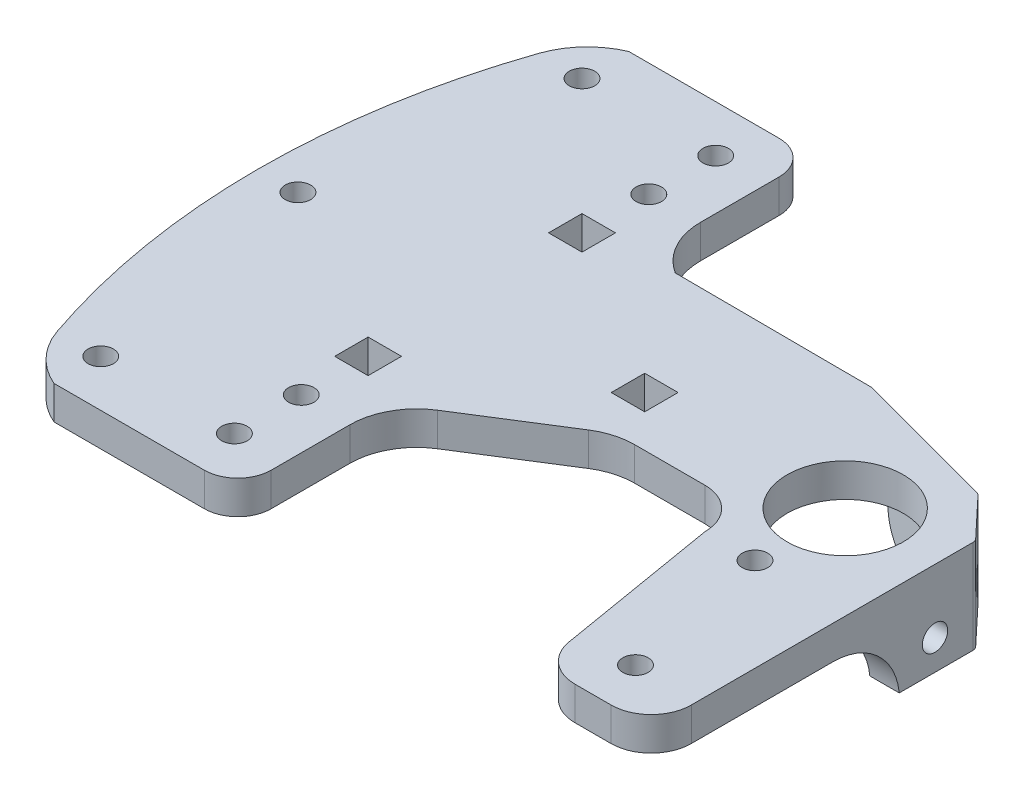
SolidWorks part; units mm, degrees
ref_plane "Front Plane" through (0, 0, 0) normal (0, 0, 1) x (1, 0, 0)
ref_plane "Top Plane" through (0, 0, 0) normal (0, 1, 0) x (1, 0, 0)
ref_plane "Right Plane" through (0, 0, 0) normal (1, 0, 0) x (0, 0, -1)
sketch "Sketch1" plane through (0, 0, 0) normal (0, 1, 0) x (1, 0, 0)
  line L0 (-7.4512, 9.6917) -> (-7.4512, -27.7227) construction
  line L3 (-37.9392, 0.1667) -> (-27.3876, 0.1667)
  line L12 (-45.5512, 12.8667) -> (-45.5512, 6.5167) construction
  line L13 (-48.7262, 6.5167) -> (-42.3762, 6.5167)
  line L14 (-48.7262, 6.5167) -> (-48.7262, 12.8667)
  line L15 (-48.7262, 12.8667) -> (-42.3762, 12.8667)
  line L16 (-42.3762, 6.5167) -> (-42.3762, 12.8667)
  line L17 (-48.7262, 6.5167) -> (-42.3762, 12.8667) construction
  line L18 (-48.7262, 12.8667) -> (-42.3762, 6.5167) construction
  line L19 (-32.6382, 30.0117) -> (-45.5512, 30.0117) construction
  line L20 (-44.7125, -1.7903) -> (-62.3286, -12.897)
  line L21 (-45.5512, 9.6917) -> (-77.7802, 30.0117) construction
  line L22 (-74.6052, -7.4533) -> (-74.6052, -13.8033)
  line L23 (-77.7802, 30.0117) -> (-77.7802, 63.0449) construction
  line L24 (-80.9552, 26.8367) -> (-74.6052, 26.8367)
  line L25 (-80.9552, 26.8367) -> (-80.9552, 33.1867)
  line L26 (-80.9552, 33.1867) -> (-74.6052, 33.1867)
  line L27 (-74.6052, 26.8367) -> (-74.6052, 33.1867)
  line L28 (-80.9552, 26.8367) -> (-74.6052, 33.1867) construction
  line L29 (-80.9552, 33.1867) -> (-74.6052, 26.8367) construction
  line L34 (-80.9552, -13.8033) -> (-74.6052, -13.8033)
  line L35 (-80.9552, -7.4533) -> (-80.9552, -13.8033)
  line L36 (-80.9552, -7.4533) -> (-74.6052, -7.4533)
  line L38 (-68.2552, -38.5683) -> (-68.2552, -23.64)
  line L39 (-18.5002, 9.6917) -> (-119.0552, 9.6917) construction
  line L43 (-119.0552, 30.0117) -> (-119.0552, 57.9517) construction
  line L45 (-103.1802, 64.3017) -> (-74.6052, 64.3017)
  line L46 (-68.2552, 57.9517) -> (-68.2552, 43.0234)
  line L48 (-119.0552, -10.6283) -> (-119.0552, -38.5683) construction
  line L49 (-103.1802, -44.9183) -> (-74.6052, -44.9183)
  line L51 (-119.0552, 30.0117) -> (-119.0552, -10.6283) construction
  line L52 (-77.7802, 55.4117) -> (-118.3701, 55.4117) construction
  line L53 (-77.7802, -36.0283) -> (-119.0552, -36.0283) construction
  line L60 (-80.9552, -10.6283) -> (-74.6052, -10.6283) construction
  line L61 (-77.7802, -10.6283) -> (-77.7802, -41.0344) construction
  line L63 (-27.3876, 0.1667) -> (-24.5537, 0.1667)
  line L64 (-16.9337, -7.4533) -> (-11.6961, -38.5634)
  line L65 (10.2916, -36.576) -> (10.2916, -37.2983)
  line L66 (2.6716, -44.9183) -> (-4.1819, -44.9183)
  line L67 (10.2916, -36.576) -> (10.2916, 31.9283)
  line L68 (10.2916, 31.9283) -> (-62.3286, 32.2804)
  line L70 (-58.7302, 30.0117) -> (-101.948, 30.0117) construction
  arc A1 (-68.2552, -23.64) -> (-62.3286, -12.897) centre (-55.5552, -23.64) cw
  circle A2 centre (-77.7802, 42.7117) radius 2.413
  circle A3 centre (-77.7802, 55.4117) radius 2.413
  arc A4 (-68.2552, 43.0234) -> (-62.3286, 32.2804) centre (-55.5552, 43.0234) ccw
  circle A5 centre (-77.7802, -23.3283) radius 2.413
  circle A6 centre (-77.7802, -36.0283) radius 2.413
  arc A7 (-119.0552, -38.5683) -> (-112.7052, -44.9183) centre (-112.7052, -38.5683) ccw construction
  arc A8 (-74.6052, -44.9183) -> (-68.2552, -38.5683) centre (-74.6052, -38.5683) ccw
  arc A9 (-74.6052, 64.3017) -> (-68.2552, 57.9517) centre (-74.6052, 57.9517) cw
  arc A10 (-112.7052, 64.3017) -> (-119.0552, 57.9517) centre (-112.7052, 57.9517) ccw construction
  arc A11 (-44.7125, -1.7903) -> (-37.9392, 0.1667) centre (-37.9392, -12.5333) cw
  circle A15 centre (-111.4352, 9.6917) radius 2.413
  circle A16 centre (-103.1802, 55.4117) radius 2.413
  circle A18 centre (-103.1802, -36.0283) radius 2.413
  circle A20 centre (-1.5802, -36.0283) radius 2.413
  circle A23 centre (-7.4512, -7.4533) radius 2.413
  arc A29 (-4.1819, -44.9183) -> (-11.6961, -38.5634) centre (-4.1819, -37.2983) cw
  arc A30 (-16.9337, -7.4533) -> (-24.5537, 0.1667) centre (-24.5537, -7.4533) ccw
  arc A31 (10.2916, -37.2983) -> (2.6716, -44.9183) centre (2.6716, -37.2983) cw
  arc A34 (-111.4352, 55.4117) -> (-111.4352, -36.0283) centre (21.9148, 9.6917) ccw
  arc A35 (-111.4352, -36.0283) -> (-103.1802, -44.9183) centre (-97.3026, -31.1828) ccw
  arc A36 (-111.4352, 55.4117) -> (-103.1802, 64.3017) centre (-97.3026, 50.5662) cw
  circle A37 centre (-7.4512, 9.6917) radius 11.049
  point P0 (-77.7802, 42.7117)
  point P4 (-7.4512, 9.6917)
  point P7 (10.9093, 16.757)
  point P8 (0, 0)
  point P11 (-45.5512, 9.6917)
  point P20 (-45.5512, 9.6917)
  point P36 (-1.8032, 31.9664)
  point P37 (-3.0768, 31.9283)
  point P38 (10.2916, 31.9283)
  point P59 (-119.0552, -44.9183)
  point P62 (-68.2552, -44.9183)
  point P65 (-68.2552, 64.3017)
  point P68 (-119.0552, 64.3017)
  point P71 (9.7971, 31.9283)
  point P99 (5.2488, -24.6633)
  point P110 (6.0398, -36.0283)
  dimension "D9" = 12.7
  dimension "D17" = 8.89
  dimension "D21" = 12.7
  dimension "D12" = 6.35
  dimension "D16" = 12.7
  dimension "D22" = 7.62
  dimension "D23" = 7.62
  dimension "D26" = 4.826
  dimension "D27" = 4.826
  dimension "D28" = 4.826
  dimension "D29" = 4.826
  dimension "D30" = 4.826
  dimension "D31" = 76.2
  dimension "D32" = 7.62
  dimension "D33" = 12.7
  dimension "D34" = 7.62
  dimension "D6" = 22.098
  dimension "D3" = 6.35
  dimension "D4" = 6.35
  dimension "D5" = 38.1
  dimension "D10" = 56.3968
  dimension "D11" = 38.1
  dimension "D13" = 6.35
  dimension "D14" = 6.35
  dimension "D15" = 12.7
  dimension "D19" = 6.35
  dimension "D20" = 38.1
  dimension "D24" = 25.4
  dimension "D25" = 25.4
extrude "Boss-Extrude1" add sketch "Sketch1" along normal blind 6.35 contours L35 L3 L16 L13 L14 L15 L27 L24 L25 L26 region at (-64.7995, 0, -7.3783)
sketch "Sketch6" plane through (0, 0, 0) normal (0, -1, 0) x (1, 0, 0)
  line L12 (10.2916, -2.2195) -> (10.2916, -16.7157)
  line L13 (10.2916, -16.7157) -> (2.7612, -24.7258)
  line L14 (10.2916, -2.2195) -> (4.7036, -2.2195)
  line L15 (-1.3101, -20.8983) -> (2.7612, -24.7258)
  line L16 (10.2916, -31.9283) -> (10.2916, 37.2983) construction
  line L17 (4.7036, -2.2195) -> (4.7036, -14.5014)
  line L18 (4.7036, -14.5014) -> (-1.3101, -20.8983)
  point P0 (0, 0)
  point P4 (0, 0)
  dimension "D1" = 5.588
  dimension "D2" = 5.588
extrude "Boss-Extrude4" add sketch "Sketch6" along normal blind 11.43 separate body
sketch "Sketch7" plane through (13.8051, 0, -12.9783) normal (0.7286, 0, -0.685) x (-0.685, 0, -0.7286)
  line L0 (5.1296, -11.43) -> (5.1296, 0) construction
  line L4 (16.1236, -11.43) -> (5.1296, -11.43) construction
  circle A0 centre (12.7496, -5.715) radius 2.413
  dimension "D1" = 4.826
  dimension "D2" = 7.62
  dimension "D3" = 5.715
extrude "Cut-Extrude4" cut sketch "Sketch7" against normal blind 11.43
sketch "Sketch8" plane through (10.2916, 0, 0) normal (1, 0, 0) x (0, 0, -1)
  line L0 (16.7157, -11.43) -> (2.2195, -11.43) construction
  line L1 (16.7157, -11.43) -> (16.7157, 0) construction
  circle A0 centre (9.0074, -5.715) radius 2.413
  dimension "D1" = 4.826
  dimension "D2" = 5.715
  dimension "D3" = 7.7083
extrude "Cut-Extrude5" cut sketch "Sketch8" against normal blind 11.43
sketch "Sketch13" plane through (0, 0, 0) normal (0, -1, 0) x (1, 0, 0)
  line L0 (-7.4512, -20.7407) -> (-7.4512, 1.3573) construction
  line L1 (-7.4512, -9.6917) -> (18.3088, -9.6917) construction
  line L2 (-7.4512, -9.6917) -> (17.698, -34.8409) construction
  line L3 (-7.4512, -8.8668) -> (1.4123, -41.9461) construction
  line L4 (2.7612, -24.7258) -> (-12.6212, -28.8475)
  line L5 (-12.6212, -28.8475) -> (-13.8508, -24.2586)
  line L6 (-13.8508, -24.2586) -> (-1.3101, -20.8983)
  line L7 (-1.3101, -20.8983) -> (2.7612, -24.7258)
  circle A0 centre (-7.4512, -9.6917) radius 11.049 construction
  dimension "D1" = 45
  dimension "D2" = 30
extrude "Boss-Extrude5" add sketch "Sketch13" along normal up to surface (11.43 mm away) up to face at (5.2403, -11.43, -13.5467)
sketch "Sketch14" plane through (6.3664, 0, -23.7598) normal (0.2588, 0, -0.9659) x (-0.9659, 0, -0.2588)
  line L1 (3.7324, -11.43) -> (3.7324, 0) construction
  circle A0 centre (10.0824, -5.7197) radius 2.3114
  point P2 (0, 0)
  point P3 (3.7324, -5.715)
  dimension "D1" = 4.6228
  dimension "D2" = 6.35
extrude "Cut-Extrude8" cut sketch "Sketch14" against normal blind 21.844
sketch "Sketch15" plane through (0, 0, 0) normal (0, -1, 0) x (1, 0, 0)
  line L0 (10.2916, -16.7157) -> (2.7612, -24.7258)
  line L1 (2.7612, -24.7258) -> (-24.7529, -32.0982)
  line L2 (10.2916, -31.9283) -> (-62.3286, -32.2804) construction
  line L3 (-24.7529, -32.0982) -> (10.2916, -31.9283)
  line L4 (10.2916, -31.9283) -> (10.2916, -16.7157)
  line L5 (-12.6212, -28.8475) -> (2.7612, -24.7258) construction
extrude "Cut-Extrude9" cut sketch "Sketch15" against normal blind 21.844
fillet "Fillet3" radius 1.27 7 edges at (-1.3101, -5.715, -20.8983) (4.7036, -5.715, -14.5014) (10.2916, -2.54, -16.7157) (2.7612, -2.54, -24.7258) (4.7036, 0, -8.3605) (1.6967, 0, -17.6999) (-7.5805, 0, -22.5784)
fillet "Fillet4" radius 5.08 1 edges at (-13.4004, 0, -25.9397)
fillet "Fillet5" radius 7.62 1 edges at (-13.236, -11.43, -26.553)
fillet "Fillet6" radius 12.7 1 edges at (6.8626, 0, -2.2195)
